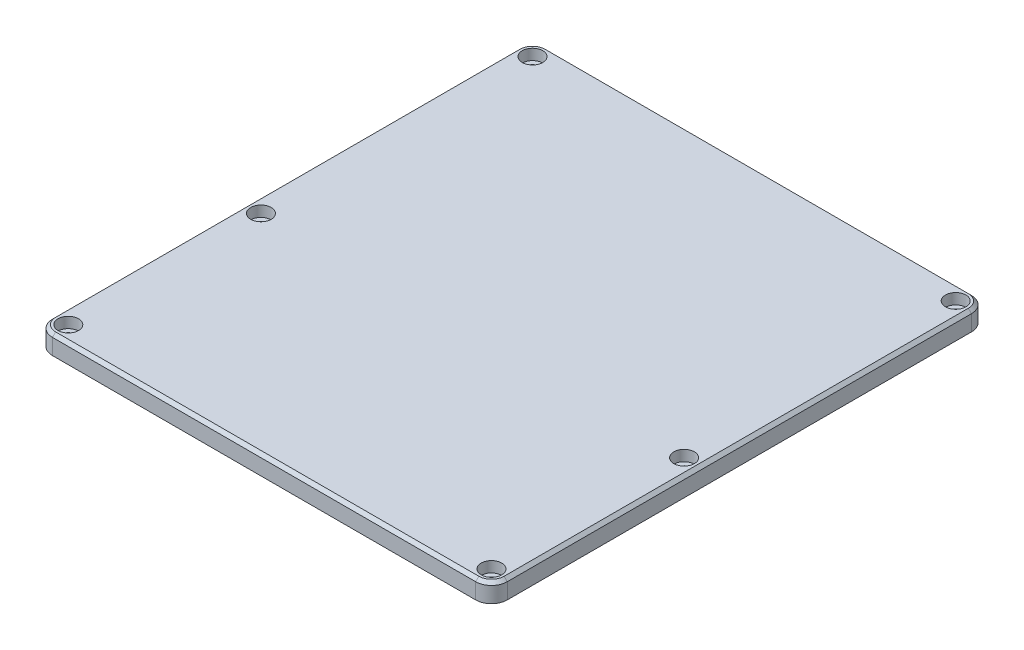
SolidWorks part; units mm, degrees
ref_plane "前视基准面" through (0, 0, 0) normal (0, 0, 1) x (1, 0, 0)
ref_plane "上视基准面" through (0, 0, 0) normal (0, 1, 0) x (1, 0, 0)
ref_plane "右视基准面" through (0, 0, 0) normal (1, 0, 0) x (0, 0, -1)
sketch "草图1" plane through (0, 0, 0) normal (0, 1, 0) x (1, 0, 0)
  line L1 (-72, -78.5) -> (72, -78.5)
  line L2 (-72, -78.5) -> (-72, 78.5)
  line L3 (-72, 78.5) -> (72, 78.5)
  line L4 (72, -78.5) -> (72, 78.5)
  line L5 (-72, -78.5) -> (72, 78.5) construction
  line L6 (-72, 78.5) -> (72, -78.5) construction
  point P0 (0, 0)
  dimension "D1" = 144
  dimension "D2" = 157
extrude "凸台-拉伸1" add sketch "草图1" along normal blind 6
fillet "圆角1" radius 5 4 edges at (72, 3, 78.5) (-72, 3, 78.5) (72, 3, -78.5) (-72, 3, -78.5)
shell "抽壳1" thickness 3 removed face at (0, 0, 0)
sketch "草图3" plane through (0, 6, 0) normal (0, 1, 0) x (1, 0, 0)
  line L0 (-62, 73.5) -> (-62, 77.0355)
  line L1 (-62, 77.0355) -> (-70.5355, 77.0355)
  line L2 (-70.5355, 77.0355) -> (-70.5355, 68.5)
  line L3 (-70.5355, 68.5) -> (-67, 68.5)
  line L4 (-72, 73.5) -> (-72, -73.5) construction
  line L5 (-67, -7.5) -> (-72, -7.5)
  line L6 (-67, -7.5) -> (-67, -17.5) construction
  line L7 (-67, -17.5) -> (-72, -17.5)
  line L8 (-72, -7.5) -> (-72, -17.5)
  line L9 (0, 0) -> (0, 27.0951) construction
  line L10 (67, -7.5) -> (67, -17.5) construction
  line L11 (72, -7.5) -> (72, -17.5)
  line L12 (67, -17.5) -> (72, -17.5)
  line L13 (67, -7.5) -> (72, -7.5)
  line L14 (70.5355, 68.5) -> (67, 68.5)
  line L15 (70.5355, 77.0355) -> (70.5355, 68.5)
  line L16 (62, 77.0355) -> (70.5355, 77.0355)
  line L17 (62, 73.5) -> (62, 77.0355)
  line L20 (0, 0) -> (-38.526, 0) construction
  line L21 (62, -73.5) -> (62, -77.0355)
  line L22 (62, -77.0355) -> (70.5355, -77.0355)
  line L23 (70.5355, -77.0355) -> (70.5355, -68.5)
  line L24 (70.5355, -68.5) -> (67, -68.5)
  line L25 (-62, -73.5) -> (-62, -77.0355)
  line L26 (-70.5355, -68.5) -> (-67, -68.5)
  line L27 (-62, -77.0355) -> (-70.5355, -77.0355)
  line L28 (-70.5355, -77.0355) -> (-70.5355, -68.5)
  arc A0 (-67, 68.5) -> (-62, 73.5) centre (-67, 73.5) ccw
  arc A1 (67, -68.5) -> (62, -73.5) centre (67, -73.5) ccw
  arc A2 (-67, -17.5) -> (-67, -7.5) centre (-67, -12.5) ccw
  arc A3 (-67, 78.5) -> (-72, 73.5) centre (-67, 73.5) ccw construction
  arc A4 (67, -17.5) -> (67, -7.5) centre (67, -12.5) cw
  arc A5 (67, 68.5) -> (62, 73.5) centre (67, 73.5) cw
  arc A6 (-67, -68.5) -> (-62, -73.5) centre (-67, -73.5) cw
  dimension "D1" = 5
  dimension "D2" = 10
  dimension "D3" = 61
  dimension "D4" = 5
extrude "凸台-拉伸2" add sketch "草图3" against normal blind 6
hole_wizard "M3 六角凹头螺钉的柱形沉头孔1" positions "草图5" profile "草图4" counterbore size "M3" standard "ISO" end condition through all
sketch "草图5" plane through (0, 6, 0) normal (0, 1, 0) x (-1, 0, 0)
  line L0 (0, 0) -> (72, 0) construction
  line L1 (72, -73.5) -> (72, 73.5) construction
  point P0 (67, 12.5)
  point P1 (67, -73.5)
  point P4 (-67, -73.5)
  point P7 (-67, 12.5)
  point P21 (-67, 73.5)
  point P22 (67, 73.5)
  dimension "D1" = 61
sketch "草图4" plane through (-67, 6, 12.5) normal (1, 0, 0) x (0, 0, 1)
  line L0 (0, 0) -> (0, 6)
  line L1 (0, 6) -> (1.7, 6)
  line L3 (1.7, 6) -> (1.7, 3.4)
  line L4 (1.7, 3.4) -> (3.25, 3.4)
  line L5 (3.25, 3.4) -> (3.25, 0)
  line L7 (3.25, 0) -> (0, 0)
  line L11 (0, -6.35) -> (0, 107.95) construction
  dimension "通孔孔直径" = 3.4
  dimension "通孔孔深度" = 6
  dimension "柱形沉头孔直径" = 6.5
  dimension "柱形沉头孔深度" = 3.4
chamfer "倒角1" distance 1 angle 45 8 edges at (-72, 6, 0) (-70.5355, 6, 77.0355) (-70.5355, 6, -77.0355) (0, 6, 78.5) (0, 6, -78.5) (70.5355, 6, 77.0355) (70.5355, 6, -77.0355) (72, 6, 0)
fillet "圆角4" radius 2 8 edges at (69, 1.5, -68.5) (62, 1.5, -75.5) (69, 1.5, 7.5) (69, 1.5, 17.5) (-69, 1.5, 17.5) (-62, 1.5, -75.5) (-69, 1.5, -68.5) (-69, 1.5, 7.5)
